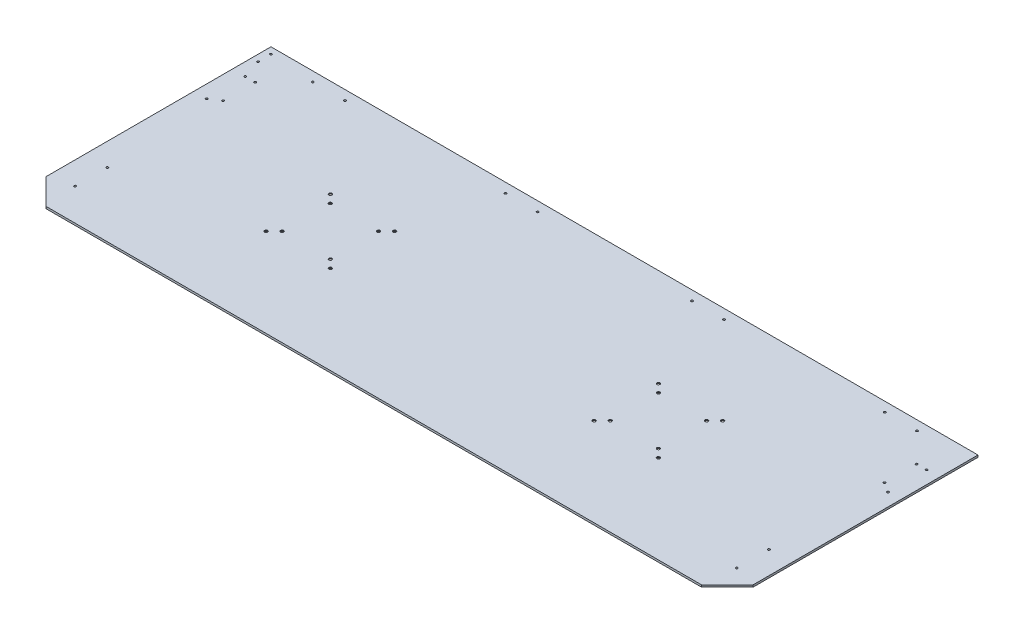
SolidWorks part; units mm, degrees
ref_plane "Front Plane" through (0, 0, 0) normal (0, 0, 1) x (1, 0, 0)
ref_plane "Top Plane" through (0, 0, 0) normal (0, 1, 0) x (1, 0, 0)
ref_plane "Right Plane" through (0, 0, 0) normal (1, 0, 0) x (0, 0, -1)
sketch "Sketch1" plane through (0, 0, 0) normal (0, 1, 0) x (1, 0, 0)
  line L1 (-550, -195) -> (550, -195)
  line L2 (-550, -195) -> (-550, 195)
  line L3 (-550, 195) -> (550, 195)
  line L4 (550, -195) -> (550, 195)
  line L5 (-550, -195) -> (550, 195) construction
  line L6 (-550, 195) -> (550, -195) construction
  point P0 (0, 0)
  dimension "D1" = 1100
  dimension "D2" = 390
extrude "Plate" add sketch "Sketch1" along normal blind 3.175
hole_wizard "Monitor Holes" positions "Sketch6" profile "Sketch7" countersink size "M4" standard "ANSI Metric" end condition through all
sketch "Sketch6" plane through (0, 0, 0) normal (0, -1, 0) x (-1, 0, 0)
  line L9 (-292.7, -44.9) -> (-217.7, -44.9)
  line L10 (-292.7, -44.9) -> (-292.7, 30.1)
  line L11 (-292.7, 30.1) -> (-217.7, 30.1)
  line L12 (-217.7, -44.9) -> (-217.7, 30.1)
  line L13 (-292.7, -44.9) -> (-217.7, 30.1) construction
  line L14 (-292.7, 30.1) -> (-217.7, -44.9) construction
  line L16 (-305.2, -57.4) -> (-205.2, -57.4)
  line L17 (-305.2, -57.4) -> (-305.2, 42.6)
  line L18 (-305.2, 42.6) -> (-205.2, 42.6)
  line L19 (-205.2, -57.4) -> (-205.2, 42.6)
  line L20 (-305.2, -57.4) -> (-205.2, 42.6) construction
  line L21 (-305.2, 42.6) -> (-205.2, -57.4) construction
  line L22 (0, 1.7463) -> (0, -1.7463) construction
  line L23 (292.7, 30.1) -> (217.7, 30.1)
  line L24 (292.7, -44.9) -> (217.7, -44.9)
  line L25 (292.7, -44.9) -> (292.7, 30.1)
  line L26 (305.2, -57.4) -> (205.2, -57.4)
  line L27 (305.2, -57.4) -> (305.2, 42.6)
  line L28 (217.7, -44.9) -> (217.7, 30.1)
  line L29 (205.2, -57.4) -> (205.2, 42.6)
  line L30 (305.2, 42.6) -> (205.2, 42.6)
  line L32 (-509.2, -159.8) -> (-1.2, -159.8)
  line L33 (-509.2, -159.8) -> (-509.2, 145)
  line L34 (-509.2, 145) -> (-1.2, 145)
  line L35 (-1.2, -159.8) -> (-1.2, 145)
  line L36 (-509.2, -159.8) -> (-1.2, 145) construction
  line L37 (-509.2, 145) -> (-1.2, -159.8) construction
  line L38 (-550, 175) -> (550, 175)
  line L39 (-550, -195) -> (-550, 195) construction
  line L40 (550, 195) -> (550, -195) construction
  line L42 (-550, 195) -> (550, 195) construction
  line L43 (0, 175) -> (0, -195)
  line L44 (550, -195) -> (-550, -195) construction
  point P80 (-217.7, 30.1)
  point P157 (-292.7, -44.9)
  point P158 (-292.7, 30.1)
  point P159 (-217.7, -44.9)
  point P161 (-205.2, 42.6)
  point P180 (-305.2, -57.4)
  point P181 (-305.2, 42.6)
  point P182 (-205.2, -57.4)
  point P186 (292.7, 30.1)
  point P187 (217.7, 30.1)
  point P188 (292.7, -44.9)
  point P189 (217.7, -44.9)
  point P190 (305.2, -57.4)
  point P191 (205.2, -57.4)
  point P192 (305.2, 42.6)
  point P193 (205.2, 42.6)
  point P307 (-255.2, -7.4)
  point P310 (-255.2, -7.4)
  point P311 (-255.2, -7.4)
  dimension "D1" = 508
  dimension "D2" = 304.8
  dimension "D3" = 20
  dimension "D4" = 75
  dimension "D5" = 100
  dimension "D6" = 40.8
  dimension "D7" = 30
sketch "Sketch7" plane through (217.7, 0, -30.1) normal (1, 0, 0) x (0, 0, -1)
  line L0 (0, 0) -> (0, 3.175)
  line L1 (0, 3.175) -> (2.4, 3.175)
  line L2 (2.4, 3.175) -> (2.4, 2.08)
  line L3 (2.4, 2.08) -> (4.48, 0)
  line L5 (4.48, 0) -> (0, 0)
  line L6 (-2.4, 2.08) -> (-4.48, 0) construction
  line L11 (0, -6.35) -> (0, 107.95) construction
  dimension "Thru Hole Dia." = 4.8
  dimension "Thru Hole Depth" = 3.175
  dimension "Near C'Sink Dia." = 8.96
  dimension "Near C'Sink Angle" = 90
hole_wizard "Strut Holes" positions "Sketch10" profile "Sketch12" tap size "M4x0.7" standard "ANSI Metric" end condition through all
sketch "Sketch10" plane through (0, 3.175, 0) normal (0, 1, 0) x (1, 0, 0)
  line L0 (-530, 135) -> (-530, 75)
  line L2 (550, 195) -> (-550, 195) construction
  line L3 (-550, 195) -> (-550, -195) construction
  line L4 (0, -1.7463) -> (0, 1.7463) construction
  line L5 (530, 135) -> (530, 75)
  point P1 (-530, 135)
  point P2 (-530, 75)
  point P11 (530, 135)
  point P12 (530, 75)
  dimension "D1" = 60
  dimension "D2" = 60
  dimension "D3" = 20
sketch "Sketch12" plane through (-530, 3.175, -135) normal (1, 0, 0) x (0, 0, 1)
  line L0 (0, 0) -> (0, 3.175)
  line L1 (0, 3.175) -> (1.65, 3.175)
  line L2 (1.65, 3.175) -> (1.65, 0)
  line L5 (1.65, 0) -> (0, 0)
  line L11 (0, -6.35) -> (0, 107.95) construction
  dimension "Thru Tap Drill Dia." = 3.3
  dimension "Thru Tap Drill Depth" = 3.175
cosmetic thread "Hole Thread1" parameters "D2"=4
cosmetic thread "Hole Thread2" parameters "D2"=4
cosmetic thread "Hole Thread3" parameters "D2"=4
cosmetic thread "Hole Thread4" parameters "D2"=4
hole_wizard "Glare Protector Holes" positions "Sketch15" profile "Sketch16" tap size "M4x0.7" standard "ANSI Metric" end condition through all
sketch "Sketch15" plane through (0, 3.175, 0) normal (0, 1, 0) x (1, 0, 0)
  line L0 (-514.6, 135) -> (-514.6, 85)
  line L2 (-514.6, -145) -> (-514.6, -95)
  line L6 (550, 195) -> (-550, 195) construction
  line L8 (-470, 180) -> (-420, 180)
  line L10 (-170, 180) -> (-120, 180)
  line L12 (420, 180) -> (470, 180)
  line L14 (120, 180) -> (170, 180)
  line L16 (-550, 195) -> (-550, -195) construction
  line L17 (550, -195) -> (550, 195) construction
  line L18 (0, -1.7463) -> (0, 1.7463) construction
  line L19 (514.6, 135) -> (514.6, 85)
  line L21 (514.6, -145) -> (514.6, -95)
  line L22 (-550, -195) -> (550, -195) construction
  point P1 (-514.6, 135)
  point P2 (-514.6, 85)
  point P5 (-514.6, -145)
  point P6 (-514.6, -95)
  point P19 (-470, 180)
  point P20 (-420, 180)
  point P23 (-170, 180)
  point P24 (-120, 180)
  point P26 (420, 180)
  point P27 (470, 180)
  point P30 (120, 180)
  point P31 (170, 180)
  point P40 (514.6, 135)
  point P41 (514.6, 85)
  point P44 (514.6, -145)
  point P45 (514.6, -95)
  dimension "D1" = 50
  dimension "D2" = 60
  dimension "D3" = 230
  dimension "D4" = 80
  dimension "D5" = 80
  dimension "D6" = 50
  dimension "D7" = 300
  dimension "D8" = 300
  dimension "D9" = 15
  dimension "D10" = 35.4
  dimension "D11" = 45
  dimension "D12" = 50
  dimension "D13" = 44.6
sketch "Sketch16" plane through (-514.6, 3.175, -135) normal (1, 0, 0) x (0, 0, 1)
  line L0 (0, 0) -> (0, 3.175)
  line L1 (0, 3.175) -> (1.65, 3.175)
  line L2 (1.65, 3.175) -> (1.65, 0)
  line L5 (1.65, 0) -> (0, 0)
  line L11 (0, -6.35) -> (0, 107.95) construction
  dimension "Thru Tap Drill Dia." = 3.3
  dimension "Thru Tap Drill Depth" = 3.175
cosmetic thread "Hole Thread5" parameters "D2"=4
cosmetic thread "Hole Thread6" parameters "D2"=4
cosmetic thread "Hole Thread9" parameters "D2"=4
cosmetic thread "Hole Thread10" parameters "D2"=4
cosmetic thread "Hole Thread11" parameters "D2"=4
cosmetic thread "Hole Thread12" parameters "D2"=4
cosmetic thread "Hole Thread13" parameters "D2"=4
cosmetic thread "Hole Thread14" parameters "D2"=4
cosmetic thread "Hole Thread15" parameters "D2"=4
cosmetic thread "Hole Thread16" parameters "D2"=4
cosmetic thread "Hole Thread17" parameters "D2"=4
cosmetic thread "Hole Thread18" parameters "D2"=4
cosmetic thread "Hole Thread21" parameters "D2"=4
cosmetic thread "Hole Thread22" parameters "D2"=4
cosmetic thread "Hole Thread23" parameters "D2"=4
cosmetic thread "Hole Thread24" parameters "D2"=4
chamfer "Chamfer1" distance 40 angle 45 2 edges at (550, 1.5875, 195) (-550, 1.5875, 195)
hole_wizard "Antenna Holes" positions "Sketch17" profile "Sketch19" tap size "M4x0.7" standard "ANSI Metric" end condition through all
sketch "Sketch17" plane through (0, 3.175, 0) normal (0, 1, 0) x (1, 0, 0)
  line L2 (-540, 165) -> (-540, 185)
  line L8 (-550, 195) -> (-550, -155) construction
  point P20 (-540, 165)
  point P21 (-540, 185)
  dimension "D1" = 20
  dimension "D2" = 10
  dimension "D4" = 10
sketch "Sketch19" plane through (-540, 3.175, -165) normal (1, 0, 0) x (0, 0, 1)
  line L0 (0, 0) -> (0, 3.175)
  line L1 (0, 3.175) -> (1.65, 3.175)
  line L2 (1.65, 3.175) -> (1.65, 0)
  line L5 (1.65, 0) -> (0, 0)
  line L11 (0, -6.35) -> (0, 107.95) construction
  dimension "Thru Tap Drill Dia." = 3.3
  dimension "Thru Tap Drill Depth" = 3.175
cosmetic thread "Hole Thread26" parameters "D2"=4
cosmetic thread "Hole Thread27" parameters "D2"=4
